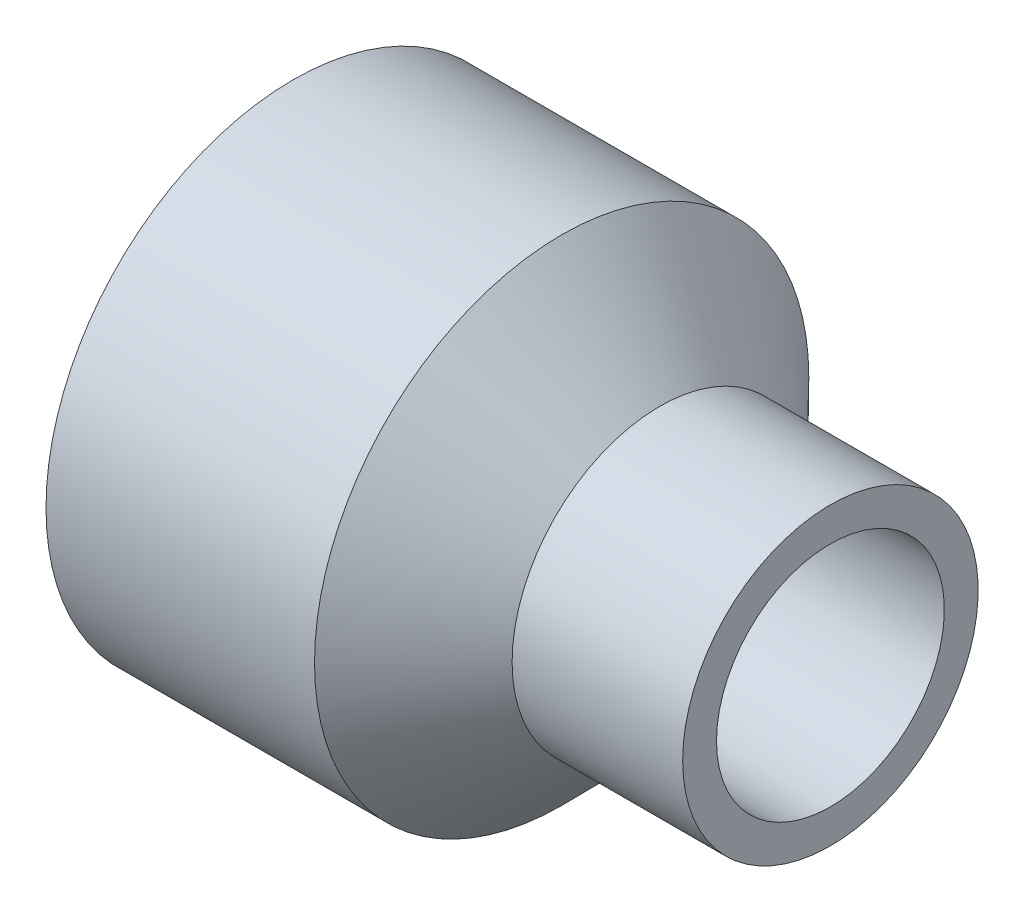
SolidWorks part; units mm, degrees
ref_plane "Front Plane" through (0, 0, 0) normal (0, 0, 1) x (1, 0, 0)
ref_plane "Top Plane" through (0, 0, 0) normal (0, 1, 0) x (1, 0, 0)
ref_plane "Right Plane" through (0, 0, 0) normal (1, 0, 0) x (0, 0, -1)
sketch "Sketch0" plane through (0, 0, 0) normal (0, 0, 1) x (1, 0, 0)
  line L0 (-39.6875, 0) -> (11.1125, 0) construction
  line L2 (-2.3812, 0) -> (11.1125, 0) construction
  line L3 (-39.6875, 0) -> (39.6875, 0) construction
  line L4 (-39.6875, 36.5125) -> (-39.6875, -36.5125) construction
  line L5 (-2.3812, 30.0863) -> (-39.6875, 30.3149) construction
  line L6 (-2.3812, 30.0863) -> (-2.3812, -30.0863) construction
  line L7 (-2.3812, -30.0863) -> (-39.6875, -30.3149) construction
  line L8 (-39.6875, 30.3149) -> (-39.6875, -30.3149) construction
  line L9 (39.6875, 16.8275) -> (39.6875, -16.8275) construction
  line L10 (39.6875, 21.8281) -> (39.6875, -21.8281) construction
  line L11 (11.1125, 12.1539) -> (11.1125, -12.1539) construction
  line L12 (11.1125, 16.637) -> (11.1125, -16.637) construction
  line L13 (11.1125, -16.637) -> (39.6875, -16.8275) construction
  line L14 (-2.3812, 24.6253) -> (-2.3812, -24.6253) construction
  line L15 (11.1125, 16.637) -> (39.6875, 16.8275) construction
  dimension "N" = 13.4937
  dimension "M" = 73.025
  dimension "OD A" = 60.6298
  dimension "OD B" = 60.1726
  dimension "ID" = 49.2506
  dimension "L" = 79.375
  dimension "ID2" = 24.3078
  dimension "OD B2" = 33.274
  dimension "OD A2" = 33.655
  dimension "M2" = 43.6562
  dimension "C" = 37.3062
  dimension "C2" = 28.575
sketch "Sketch1" plane through (0, 0, 0) normal (0, 0, 1) x (1, 0, 0)
  line L0 (-39.6875, 0) -> (11.1125, 0) construction
  line L1 (-39.6875, 0) -> (11.1125, 0) construction
  line L2 (-2.3812, -30.0863) -> (13.1185, -14.3954) construction
  line L3 (0, -36.4946) -> (-4.4091, -32.1392) construction
  line L4 (-39.6875, -36.5125) -> (-39.6875, -30.3149)
  line L5 (-39.6875, -30.3149) -> (-2.3812, -30.0863)
  line L6 (11.1125, -14.3954) -> (8.8433, -14.3954) construction
  line L7 (8.8433, -14.3954) -> (11.1125, -16.637) construction
  line L8 (-0.0177, -36.5125) -> (14.4878, -21.8281)
  line L9 (-0.0177, -36.5125) -> (-39.6875, -36.5125)
  line L10 (0, 0) -> (0, -36.4946) construction
  line L11 (8.8433, -14.3954) -> (13.1185, -14.3954) construction
  line L12 (11.1125, -16.637) -> (39.6875, -16.8275)
  line L13 (39.6875, -16.8275) -> (39.6875, -21.8281)
  line L14 (39.6875, -21.8281) -> (14.4878, -21.8281)
  line L15 (11.1125, -12.1539) -> (11.1125, -16.637) construction
  line L16 (11.1125, -16.637) -> (8.8433, -14.3954)
  line L17 (8.8433, -14.3954) -> (-2.3812, -30.0863)
  dimension "D1" = 45
revolve "Revolve1" add sketch "Sketch1" angle 360 about L1
